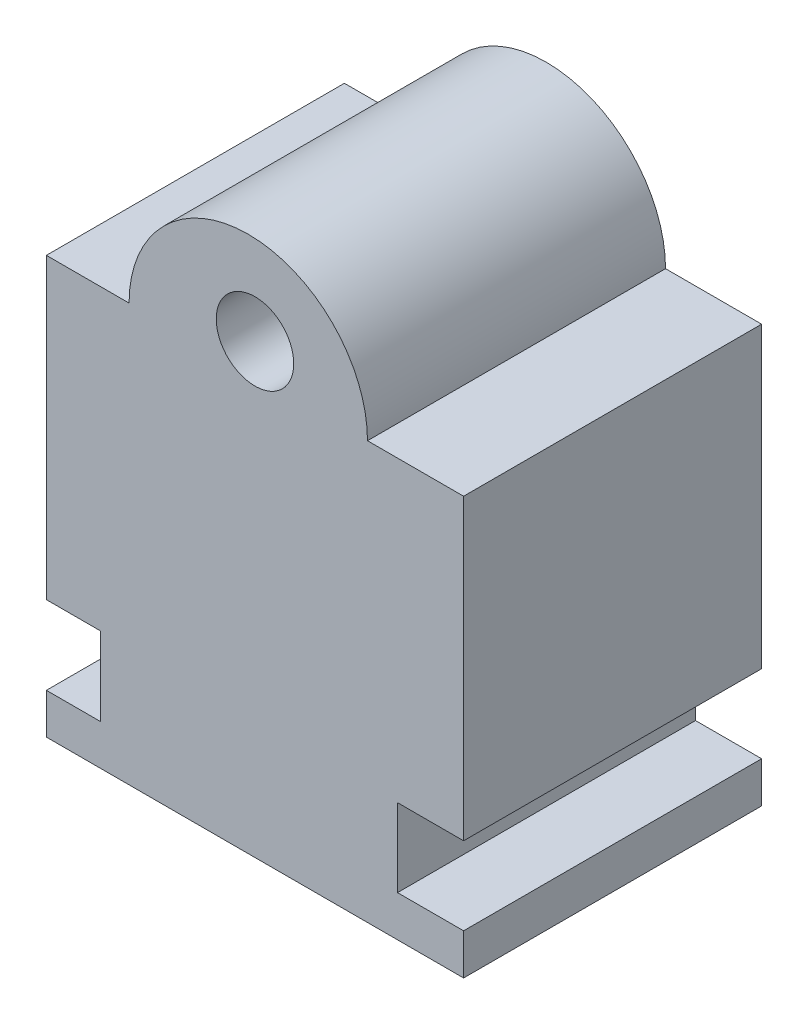
SolidWorks part; units mm, degrees
ref_plane "Plan de face" through (0, 0, 0) normal (0, 0, 1) x (1, 0, 0)
ref_plane "Plan de dessus" through (0, 0, 0) normal (0, 1, 0) x (1, 0, 0)
ref_plane "Plan de droite" through (0, 0, 0) normal (1, 0, 0) x (0, 0, -1)
sketch "Esquisse1" plane through (0, 0, 0) normal (0, 0, 1) x (1, 0, 0)
  line L0 (0, 0) -> (700, 0)
  line L1 (700, 0) -> (700, 450)
  line L2 (700, 450) -> (538.7581, 450)
  line L3 (0, 0) -> (0, 450)
  line L4 (0, 450) -> (138.7581, 450)
  arc A0 (538.7581, 450) -> (138.7581, 450) centre (338.7581, 450) ccw
  dimension "D3" = 200
  dimension "D1" = 700
  dimension "D2" = 450
extrude "Boss.-Extru.1" add sketch "Esquisse1" along normal blind 500
sketch "Esquisse2" plane through (0, 0, 0) normal (0, -1, 0) x (1, 0, 0)
  line L0 (700, 500) -> (700, 0)
  line L1 (700, 0) -> (0, 0)
  line L2 (0, 0) -> (0, 500)
  line L3 (0, 500) -> (700, 500) construction
  line L4 (0, 500) -> (0, 0) construction
  line L5 (0, 500) -> (700, 500)
extrude "Boss.-Extru.2" add sketch "Esquisse2" along normal blind 250
sketch "Esquisse3" plane through (0, 0, 0) normal (0, 0, -1) x (-1, 0, 0)
  circle A0 centre (-350, 500) radius 65
extrude "Enlèv. mat.-Extru.1" cut sketch "Esquisse3" against normal blind 500
sketch "Esquisse4" plane through (0, 0, 0) normal (0, 0, -1) x (-1, 0, 0)
  line L0 (0, -50.3189) -> (-91.0727, -50.3189)
  line L1 (0, 450) -> (0, -250) construction
  line L2 (-91.0727, -50.3189) -> (-91.0727, -181.9886)
  line L3 (-91.0727, -181.9886) -> (0, -181.9886)
  line L4 (0, -181.9886) -> (0, -50.3189)
extrude "Enlèv. mat.-Extru.2" cut sketch "Esquisse4" against normal blind 500
sketch "Esquisse5" plane through (0, 0, 0) normal (0, 0, -1) x (-1, 0, 0)
  line L0 (-700, -181.4044) -> (-589.1123, -181.4044)
  line L1 (-700, -250) -> (-700, 450) construction
  line L2 (-589.1123, -181.4044) -> (-589.1123, -50.6587)
  line L3 (-589.1123, -50.6587) -> (-700, -50.6587)
  line L4 (-700, -50.6587) -> (-700, -181.4044)
extrude "Enlèv. mat.-Extru.3" cut sketch "Esquisse5" against normal blind 500
